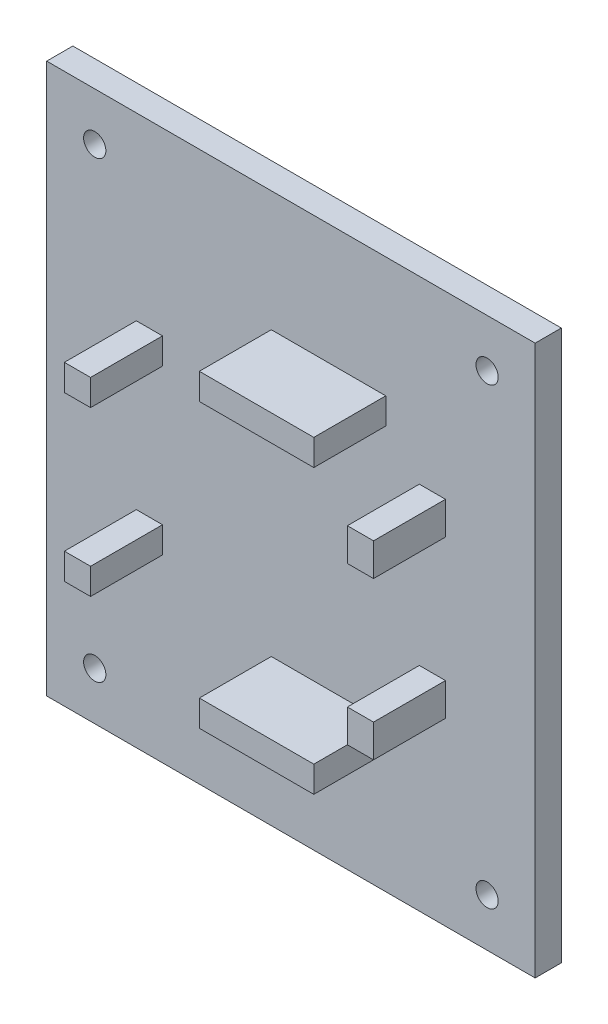
SolidWorks part; units mm, degrees
material "Cast Alloy Steel"
ref_plane "Front Plane" through (0, 0, 0) normal (0, 0, 1) x (1, 0, 0)
ref_plane "Top Plane" through (0, 0, 0) normal (0, 1, 0) x (1, 0, 0)
ref_plane "Right Plane" through (0, 0, 0) normal (1, 0, 0) x (0, 0, -1)
sketch "Sketch2" plane through (0, 0, 0) normal (0, 0, 1) x (1, 0, 0)
  line L1 (-37.335, 42.025) -> (37.335, 42.025)
  line L2 (-37.335, 42.025) -> (-37.335, -42.025)
  line L3 (-37.335, -42.025) -> (37.335, -42.025)
  line L4 (37.335, 42.025) -> (37.335, -42.025)
  line L5 (0, -42.025) -> (0, 42.025) construction
  line L6 (-37.335, 0) -> (37.335, 0) construction
  line L14 (19.5, -19.5) -> (19.5, 19.5) construction
  line L15 (14.5, -19.63) -> (-3, -19.63)
  line L16 (14.5, -19.63) -> (14.5, -23.63)
  line L17 (14.5, -23.63) -> (-3, -23.63)
  line L18 (19.63, -19.63) -> (19.63, 19.63)
  line L19 (19.63, 19.63) -> (-19.63, 19.63)
  line L20 (-19.63, 19.63) -> (-19.63, -19.63)
  line L21 (-19.63, -19.63) -> (19.63, -19.63)
  line L22 (19.63, -19.63) -> (19.63, 19.63)
  line L23 (19.63, 19.63) -> (-19.63, 19.63)
  line L24 (-19.63, 19.63) -> (-19.63, -19.63)
  line L25 (-19.63, -19.63) -> (19.63, -19.63)
  line L26 (-3, -19.63) -> (-3, -23.63)
  line L27 (5.75, -23.63) -> (5.75, -19.63) construction
  line L28 (14.5, -21.63) -> (-3, -21.63) construction
  line L29 (19.63, -14.5) -> (23.63, -14.5)
  line L30 (19.63, -14.5) -> (19.63, -9.5)
  line L31 (19.63, -9.5) -> (23.63, -9.5)
  line L32 (23.63, -14.5) -> (23.63, -9.5)
  line L33 (21.63, -9.5) -> (21.63, -14.5) construction
  line L34 (19.63, -12) -> (23.63, -12) construction
  line L35 (19.63, 14.5) -> (23.63, 14.5)
  line L36 (19.63, 14.5) -> (19.63, 9.5)
  line L37 (19.63, 9.5) -> (23.63, 9.5)
  line L38 (23.63, 14.5) -> (23.63, 9.5)
  line L39 (21.63, 9.5) -> (21.63, 14.5) construction
  line L40 (19.63, 12) -> (23.63, 12) construction
  line L41 (14.5, 19.63) -> (-3, 19.63)
  line L42 (14.5, 19.63) -> (14.5, 23.63)
  line L43 (14.5, 23.63) -> (-3, 23.63)
  line L44 (-3, 19.63) -> (-3, 23.63)
  line L45 (5.75, 23.63) -> (5.75, 19.63) construction
  line L46 (14.5, 21.63) -> (-3, 21.63) construction
  line L47 (-19.63, 14.5) -> (-23.63, 14.5)
  line L48 (-19.63, 14.5) -> (-19.63, 10.5)
  line L49 (-19.63, 10.5) -> (-23.63, 10.5)
  line L50 (-23.63, 14.5) -> (-23.63, 10.5)
  line L51 (-21.63, 10.5) -> (-21.63, 14.5) construction
  line L52 (-19.63, 12.5) -> (-23.63, 12.5) construction
  line L53 (-19.63, -14.5) -> (-23.63, -14.5)
  line L54 (-19.63, -14.5) -> (-19.63, -10.5)
  line L55 (-19.63, -10.5) -> (-23.63, -10.5)
  line L56 (-23.63, -14.5) -> (-23.63, -10.5)
  line L57 (-21.63, -10.5) -> (-21.63, -14.5) construction
  line L58 (-19.63, -12.5) -> (-23.63, -12.5) construction
  line L59 (-19.5, -19.5) -> (19.5, -19.5) construction
  line L60 (19.5, 19.5) -> (-19.5, 19.5) construction
  circle A0 centre (-29.99, 34.68) radius 1.7
  circle A1 centre (29.99, 34.68) radius 1.7
  circle A2 centre (29.99, -34.68) radius 1.7
  circle A3 centre (-29.99, -34.68) radius 1.7
  point P44 (21.63, -12)
  point P61 (5.75, 21.63)
  point P70 (-21.63, -12.5)
  point P77 (21.63, 12)
  point P96 (5.75, -21.63)
  point P100 (-21.63, 12.5)
  point P184 (0, 0)
  circle M1 centre (29.99, 34.68) radius 2.75
  line M2 (25.365, 39.305) -> (25.365, 30.055)
  line M3 (25.365, 30.055) -> (34.615, 30.055)
  line M4 (34.615, 30.055) -> (34.615, 39.305)
  line M5 (34.615, 39.305) -> (25.365, 39.305)
  dimension "D1" = 3.4
  dimension "D2" = 3.4
  dimension "D3" = 3.4
  dimension "D4" = 3.4
  dimension "D6" = 4
  dimension "D7" = 4
  dimension "D8" = 4
  dimension "D9" = 4
  dimension "D10" = 4
  dimension "D11" = 4
  dimension "D12" = 17.5
  dimension "D13" = 5
  dimension "D14" = 17.5
  dimension "D15" = 5
  dimension "D16" = 4
  dimension "D17" = 5
  dimension "D18" = 4
  dimension "D19" = 5
  dimension "D20" = 5
  dimension "D21" = 5
  dimension "D22" = 5
  dimension "D23" = 5
  dimension "D5" = 0.13
extrude "Boss-Extrude1" add sketch "Sketch2" along normal blind 4 contours L4 L1 L2 L3 A3 A2 A0 L53 L56 L55 L24 L49 L50 L47 L23 L44 L43 L42 L22 L35 L38 L37 L31 L32 L29 L25 L16 L17 L26 M2 M5 M4 M3 | L15 L26 L17 L16 | L29 L32 L31 L22 | L24 L25 L15 L22 L23 | L38 L35 L22 L37 | L44 L23 L42 L43 | L47 L50 L49 L24 | L56 L53 L24 L55 | A1 M1 | M5 M2 M3 M4 M1 region at (0, 40.9007, 0) region at (5.75, -21.63, 0) region at (0, 0, 0) region at (21.63, -12, 0) region at (-21.63, -12.5, 0) region at (21.63, 12, 0) region at (-21.63, 12.5, 0) region at (5.75, 21.63, 0) region at (27.3178, 34.68, 0) region at (29.99, 39.1742, 0)
extrude "Boss-Extrude2" add sketch "Sketch2<3>" along normal blind 15 contours L15 L26 L17 L16 | L56 L53 L24 L55 | L44 L23 L42 L43 | L29 L32 L31 L22 | L49 L50 L47 L48 | L37 L38 L35 L36 region at (5.75, -21.63, 0) region at (21.63, -12, 0) region at (-21.63, -12.5, 0) region at (5.75, 21.63, 0)
sketch "Sketch2<3>" plane through (0, 0, 0) normal (0, 0, 1) x (1, 0, 0) same geometry as "Sketch2"
